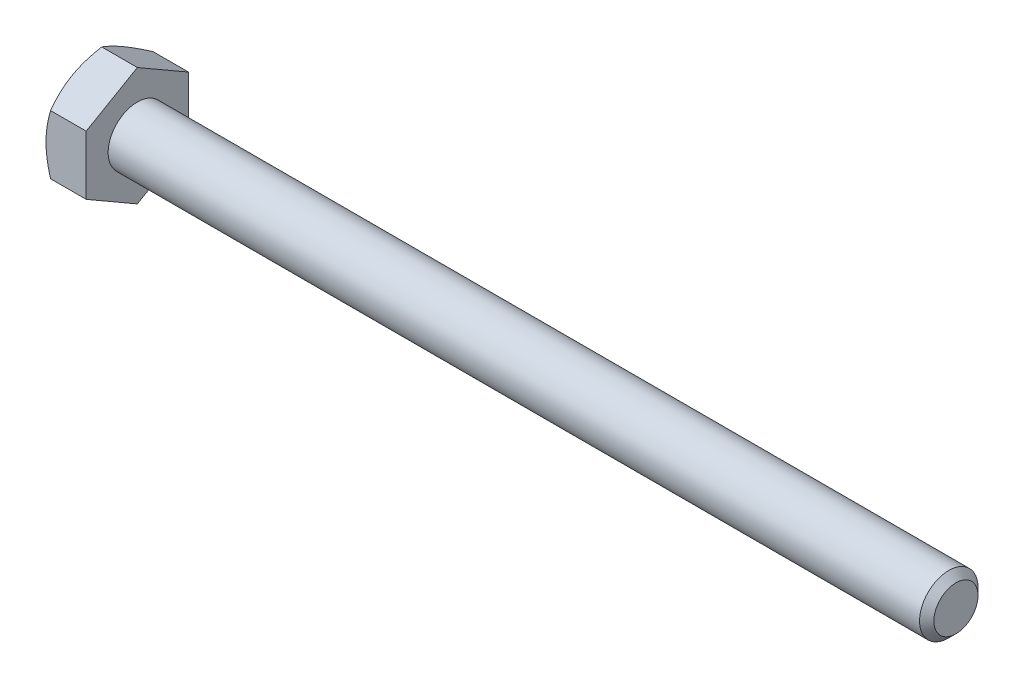
SolidWorks part; units mm, degrees
material "Alloy Steel"
ref_plane "Front Plane" through (0, 0, 0) normal (0, 0, 1) x (1, 0, 0)
ref_plane "Top Plane" through (0, 0, 0) normal (0, 1, 0) x (1, 0, 0)
ref_plane "Right Plane" through (0, 0, 0) normal (1, 0, 0) x (0, 0, -1)
sketch "Sketch1" plane through (0, 0, 0) normal (0, 0, 1) x (1, 0, 0)
  line L0 (-46.6328, 0) -> (46.6328, 0) construction
  line L1 (46.6328, 3.175) -> (46.6328, -3.175) construction
  line L2 (-42.2672, 5.5562) -> (-42.2672, -5.5562) construction
  line L3 (-46.6328, 5.5562) -> (-46.6328, -5.5562) construction
  point P9 (-42.2672, 0)
  point P10 (42.1878, -3.175)
  dimension "D1" = 4.445
  dimension "Screw Dia" = 6.35
  dimension "Hex" = 11.1125
  dimension "Head Ht" = 4.3656
  dimension "Screw Lenght" = 88.9
ref_plane "Plane2" through (46.6328, 0, 0) normal (1, 0, 0) x (0, 0, -1)
sketch "Sketch5" plane through (46.6328, 0, 0) normal (1, 0, 0) x (0, 0, -1)
  circle A0 centre (0, 0) radius 3.175
extrude "Boss-Extrude3" add sketch "Sketch5" against normal up to vertex (88.9 mm away) up to point (-42.2672, 0, 0)
sketch "Sketch9" plane through (46.6328, 0, 0) normal (1, 0, 0) x (0, 0, -1)
  circle A1 centre (0, 0) radius 3.175
  circle A2 centre (0, 0) radius 3.175
  dimension "D1" = 0
curve "Helix/Spiral1" [suppressed] pitch 1.27 height 90.17 turns 71 parameters "Pitch"=1.27
chamfer "Chamfer1" distance 0.7772 angle 45 1 edges at (46.6328, 0, -3.175)
sketch "Sketch10" plane through (0, 0, 0) normal (0, 0, 1) x (1, 0, 0)
  line L0 (46.6328, 3.175) -> (47.1091, 2.3501)
  line L1 (47.1091, 2.3501) -> (47.2678, 2.3501)
  line L2 (47.2678, 2.3501) -> (47.7441, 3.175)
  line L3 (46.6328, 3.175) -> (47.7441, 3.175)
  line L4 (47.1884, 3.175) -> (47.1884, 2.3501) construction
  line L5 (46.8709, 2.7626) -> (47.5059, 2.7626) construction
  dimension "D1" = 60
  dimension "D2" = 0.1588
  dimension "D3" = 0.635
sweep "Cut-Sweep1" [suppressed] cut profiles "Sketch10" path "Helix/Spiral1"
sketch "Sketch6" plane through (-42.2672, 0, 0) normal (-1, 0, 0) x (0, 0, 1)
  line L0 (0, 5.5562) -> (0, -5.5562) construction
  line L1 (5.5563, 3.2079) -> (0, 6.4158)
  line L2 (0, 6.4158) -> (-5.5562, 3.2079)
  line L3 (-5.5562, 3.2079) -> (-5.5562, -3.2079)
  line L4 (-5.5562, -3.2079) -> (0, -6.4158)
  line L5 (0, -6.4158) -> (5.5563, -3.2079)
  line L6 (5.5563, -3.2079) -> (5.5563, 3.2079)
  circle A0 centre (0, 0) radius 5.5563 construction
extrude "Boss-Extrude4" add sketch "Sketch6" along normal up to vertex (4.3656 mm away) up to point (-46.6328, -5.5562, 0)
sketch "Sketch7" plane through (-46.6328, 0, 0) normal (-1, 0, 0) x (0, 0, 1)
  circle A0 centre (0, 0) radius 5.5563 construction
  circle A1 centre (0, 0) radius 5.5563
sketch "Sketch8" plane through (-46.6328, 0, 0) normal (-1, 0, 0) x (0, 0, 1)
  circle A0 centre (0, 0) radius 5.5563 construction
  circle A1 centre (0, 0) radius 5.5563
extrude "Cut-Extrude3" cut sketch "Sketch8" against normal through all draft 60 flip side to cut
sketch "Sketch12" plane through (-46.6328, 0, 0) normal (-1, 0, 0) x (0, 0, 1)
  line L0 (0, 4.2783) -> (0, 2.3892) construction
  line L1 (0.1667, 4.2783) -> (0.1667, 2.3892)
  line L2 (-0.1667, 4.2783) -> (-0.1667, 2.3892)
  line L3 (0, 3.175) -> (0, -3.175) construction
  arc A0 (0.1667, 4.2783) -> (-0.1667, 4.2783) centre (0, 4.2783) ccw
  arc A1 (-0.1667, 2.3892) -> (0.1667, 2.3892) centre (0, 2.3892) ccw
  circle A3 centre (0, 0) radius 2.2225 construction
  circle A4 centre (0, 0) radius 4.445 construction
  point P2 (0, 3.3337)
  dimension "D1" = 4.445
  dimension "D3" = 8.89
  dimension "D2" = 0.3334
extrude "Cut-Extrude4" cut sketch "Sketch12" against normal blind 0.254
pattern_circular "CirPattern1" count 3 over 360 about axis through (-42.2672, 0, 0) along (1, 0, 0) of "Cut-Extrude4"
equation "\"D2@Sketch10\" = \"Pitch@Helix/Spiral1\"*.125"
equation "\"D3@Sketch10\" = \"Pitch@Helix/Spiral1\"*.5"
equation "\"D1@Chamfer1\" = \"Pitch@Helix/Spiral1\"*.612"
equation "\"D1@Sketch12\" = \"Hex@Sketch1\"*.4"
equation "\"D3@Sketch12\" = \"Hex@Sketch1\"*.8"
equation "\"D2@Sketch12\" = \"Hex@Sketch1\"*.03"
equation "\"D1@Sketch1\" = \"Pitch@Helix/Spiral1\"*3.5"
equation "\"D3@Helix/Spiral1\" = \"Screw Lenght@Sketch1\"+\"Pitch@Helix/Spiral1\""
